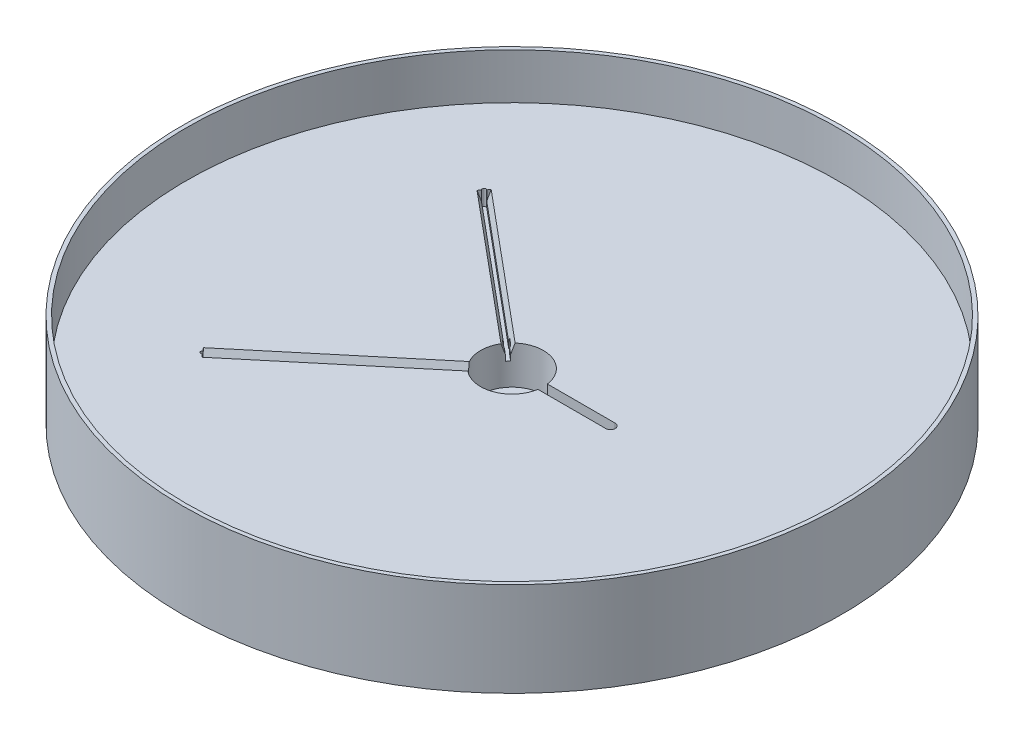
SolidWorks part; units mm, degrees
ref_plane "Front Plane" through (0, 0, 0) normal (0, 0, 1) x (1, 0, 0)
ref_plane "Top Plane" through (0, 0, 0) normal (0, 1, 0) x (1, 0, 0)
ref_plane "Right Plane" through (0, 0, 0) normal (1, 0, 0) x (0, 0, -1)
sketch "Sketch1" plane through (0, 0, 0) normal (0, 1, 0) x (1, 0, 0)
  circle A0 centre (0, 0) radius 266.7
extrude "Boss-Extrude1" add sketch "Sketch1" along normal blind 76.2
sketch "Sketch2" plane through (0, 76.2, 0) normal (0, 1, 0) x (1, 0, 0)
  circle A0 centre (0, 0) radius 263.525
extrude "Cut-Extrude1" cut sketch "Sketch2" against normal blind 37.084
sketch "Sketch3" plane through (0, 39.116, 0) normal (0, 1, 0) x (1, 0, 0)
  circle A0 centre (0, 0) radius 25.4
extrude "Cut-Extrude2" cut sketch "Sketch3" against normal blind 30.988
sketch "Sketch4" plane through (0, 39.116, 0) normal (0, 1, 0) x (1, 0, 0)
  line L0 (3.81, -0.2983) -> (80.01, -0.2983) construction
  line L1 (0, 3.5117) -> (76.2, 3.5117) construction
  line L2 (0, 3.5117) -> (0, -4.1083) construction
  line L3 (0, -4.1083) -> (76.2, -4.1083) construction
  line L4 (76.2, 3.5117) -> (76.2, -4.1083) construction
  line L5 (3.81, 3.5117) -> (80.01, 3.5117)
  line L6 (3.81, -4.1083) -> (80.01, -4.1083)
  line L7 (0, 3.5117) -> (0, -4.1083) construction
  arc A0 (3.81, 3.5117) -> (3.81, -4.1083) centre (3.81, -0.2983) ccw
  arc A1 (80.01, -4.1083) -> (80.01, 3.5117) centre (80.01, -0.2983) ccw
  point P6 (41.91, -0.2983)
extrude "Cut-Extrude3" cut sketch "Sketch4" against normal through all
sketch "Sketch5" plane through (0, 39.116, 0) normal (0, 1, 0) x (1, 0, 0)
  line L0 (0, 0) -> (-39.9134, 33.31) construction
  line L1 (-39.9134, 33.31) -> (-39.9134, -33.31) construction
  line L2 (-39.9134, 0) -> (-42.73, -2.8166) construction
  line L3 (0, 0) -> (-39.9134, 0) construction
  line L4 (-39.9134, 0) -> (-42.73, 2.8166) construction
  line L5 (0, 0) -> (-39.9134, -33.31) construction
  line L6 (0, 0) -> (-136.5075, 113.9234) construction
  line L7 (-0.9765, -1.1701) -> (-137.484, 112.7533)
  line L8 (0.9765, 1.1701) -> (-135.5311, 115.0934)
  line L13 (0, 0) -> (-136.5075, -113.9234) construction
  line L14 (-136.5075, -113.9234) -> (0, 0) construction
  line L15 (-137.484, -112.7533) -> (-0.9765, 1.1701)
  line L16 (-135.5311, -115.0934) -> (0.9765, -1.1701)
  arc A0 (-0.9765, -1.1701) -> (0.9765, 1.1701) centre (0, 0) ccw
  arc A1 (-135.5311, 115.0934) -> (-137.484, 112.7533) centre (-136.5075, 113.9234) ccw
  arc A4 (-137.484, -112.7533) -> (-135.5311, -115.0934) centre (-136.5075, -113.9234) ccw
  arc A5 (0.9765, -1.1701) -> (-0.9765, 1.1701) centre (0, 0) ccw
  point P7 (-68.2538, 56.9617)
  point P24 (-68.2538, -56.9617)
  arc M12 (25.0655, -4.1083) -> (25.1561, 3.5117) centre (0, 0) cw
extrude "Cut-Extrude4" cut sketch "Sketch5" against normal blind 12.7 contours L15 A4 L16 M12 | L7 A1 L8 A0 region at (-78.4582, 39.116, 65.4779)
ref_plane "Plane1" through (-19.4659, 0, -16.2454) normal (0.7678, 0, 0.6407) x (0.6407, 0, -0.7678)
sketch "Sketch6" plane through (-19.4659, 0, -16.2454) normal (0.7678, 0, 0.6407) x (0.6407, 0, -0.7678)
  line L0 (0, 26.416) -> (-4.0671, 39.116)
  line L1 (1.524, 26.416) -> (-1.524, 26.416) construction
  line L2 (-1.524, 39.116) -> (-24.6725, 39.116) construction
  line L3 (-4.0671, 39.116) -> (4.0671, 39.116)
  line L4 (1.524, 39.116) -> (-1.524, 39.116) construction
  line L5 (0, 39.116) -> (0, 26.416) construction
  line L6 (0, 26.416) -> (4.0671, 39.116)
extrude "Cut-Extrude5" cut sketch "Sketch6" against normal blind 152.4 and the other way blind 6.35
ref_plane "Plane2" through (-19.4659, 0, 16.2454) normal (-0.7678, 0, 0.6407) x (0.6407, 0, 0.7678)
sketch "Sketch11" plane through (-19.4659, 0, 16.2454) normal (-0.7678, 0, 0.6407) x (0.6407, 0, 0.7678)
  line L0 (0, 26.416) -> (4.7515, 39.116)
  line L1 (1.524, 26.416) -> (-1.524, 26.416) construction
  line L2 (263.525, 39.116) -> (-263.525, 39.116) construction
  line L3 (4.7515, 39.116) -> (-4.7515, 39.116)
  line L5 (0, 39.4107) -> (0, 26.416) construction
  line L7 (0, 26.416) -> (-4.7515, 39.116)
extrude "Cut-Extrude6" cut sketch "Sketch11" along normal blind 152.4 and the other way blind 6.35
ref_plane "Plane3" through (-24.3412, 0, 20.3141) normal (-0.7678, 0, 0.6407) x (0.6407, 0, 0.7678)
sketch "Sketch12" plane through (-24.3412, 0, 20.3141) normal (-0.7678, 0, 0.6407) x (0.6407, 0, 0.7678)
  line L0 (0, 26.416) -> (0, 31.0485) construction
  line L1 (1.524, 26.416) -> (-1.524, 26.416) construction
  line L2 (2.159, 26.416) -> (-2.159, 26.416) construction
  line L4 (-2.159, 26.416) -> (2.159, 26.416)
  line L7 (-2.159, 26.416) -> (-2.159, 41.4963)
  line L8 (-2.159, 41.4963) -> (2.159, 41.4963)
  line L9 (2.159, 26.416) -> (2.159, 41.4963)
extrude "Cut-Extrude10" cut sketch "Sketch12" along normal blind 6.35
ref_plane "Plane4" through (-24.3412, 0, -20.3141) normal (0.7678, 0, 0.6407) x (0.6407, 0, -0.7678)
sketch "Sketch14" plane through (-24.3412, 0, -20.3141) normal (0.7678, 0, 0.6407) x (0.6407, 0, -0.7678)
  line L0 (-2.159, 39.116) -> (2.159, 39.116) construction
  line L1 (0, 26.416) -> (-2.159, 26.416) construction
  line L2 (1.524, 26.416) -> (-1.524, 26.416) construction
  line L3 (-2.159, 26.416) -> (-2.159, 39.116) construction
  line L4 (2.159, 39.116) -> (2.159, 26.416) construction
  line L5 (2.159, 26.416) -> (0, 26.416) construction
  line L6 (0, 26.416) -> (-0.0449, 26.4266) construction
  line L8 (-2.159, 39.116) -> (2.159, 39.116)
  line L9 (-2.159, 39.116) -> (-2.159, 26.416)
  line L10 (-2.159, 26.416) -> (2.159, 26.416)
  line L11 (2.159, 39.116) -> (2.159, 26.416)
extrude "Cut-Extrude11" cut sketch "Sketch14" against normal blind 6.35
sketch "Sketch15" plane through (0, 39.116, 0) normal (0, 1, 0) x (1, 0, 0)
  circle A0 centre (0, 0) radius 177.8 construction
  circle A1 centre (-160.8582, 0) radius 16.9418 construction
